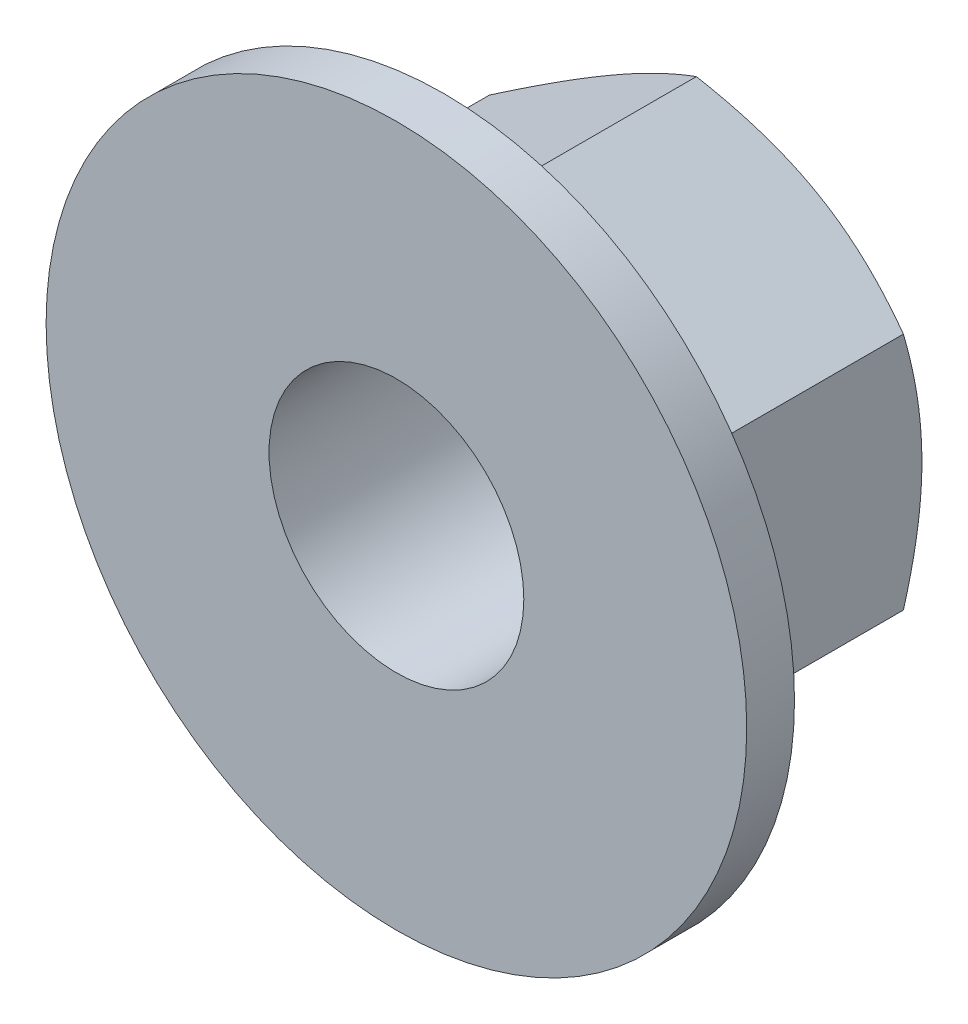
SolidWorks part; units mm, degrees
ref_plane "Plan1" through (0, 0, 0) normal (0, 0, 1) x (1, 0, 0)
ref_plane "Plan2" through (0, 0, 0) normal (0, 1, 0) x (1, 0, 0)
ref_plane "Plan3" through (0, 0, 0) normal (1, 0, 0) x (0, 0, -1)
sketch "Esquisse1" plane through (0, 0, 0) normal (0, 0, 1) x (1, 0, 0)
  line L0 (0, 0) -> (6.5, 0) construction
  line L1 (6.5, -3.7528) -> (6.5, 3.7528)
  line L2 (0, 0) -> (6.5, 3.7528) construction
  line L3 (0, 0) -> (0, 7.5056) construction
  line L4 (6.5, 3.7528) -> (0, 7.5056)
  line L5 (6.5, -3.7528) -> (0, -7.5056)
  line L6 (-6.5, -3.7528) -> (0, -7.5056)
  line L7 (-6.5, -3.7528) -> (-6.5, 3.7528)
  line L8 (-6.5, 3.7528) -> (0, 7.5056)
  circle A0 centre (0, 0) radius 6.5 construction
  circle A1 centre (0, 0) radius 7.5056 construction
  dimension "D2" = 13
  dimension "D1" = 30
extrude "Base-Extrusion" add sketch "Esquisse1" against normal blind 10
sketch "Esquisse2" plane through (0, 0, 0) normal (0, 1, 0) x (1, 0, 0)
  line L1 (0, 10) -> (0, 0) construction
  line L2 (-6.5, 10) -> (-23.8205, 10)
  line L3 (-23.8205, 10) -> (-23.8205, 0)
  line L5 (-23.8205, 0) -> (-6.5, 10)
  line L6 (0, 10) -> (0, 0) construction
  dimension "D1" = 30
revolve "Enlèvement de matière-Révolution1" cut sketch "Esquisse2" angle 360 about L6
sketch "Esquisse3" plane through (0, 0, 0) normal (0, 0, 1) x (1, 0, 0)
  circle A0 centre (0, 0) radius 4
  dimension "D1" = 8
extrude "Enlèv. mat.-Extru.1" cut sketch "Esquisse3" against normal through all
ref_axis "Axe1" through (0, 0, -50) along (0, 0, 1)
sketch "Esquisse4" plane through (0, 0, 0) normal (0, 1, 0) x (1, 0, 0)
  line L0 (-6.5, 0) -> (-11, 0)
  line L1 (-11, 0) -> (-11, 1.5)
  line L2 (-11, 1.5) -> (-8, 3)
  line L4 (-6.5, 3.5) -> (-6.5, 0)
  line L5 (-8, 3) -> (-8, 3.5)
  line L6 (0, 0) -> (0, 10) construction
  line L7 (0, 10) -> (0, 0) construction
  line L8 (-8, 3.5) -> (-6.5, 3.5)
  dimension "D4" = 3
  dimension "D5" = 3.5
  dimension "D1" = 22
  dimension "D2" = 16
  dimension "D3" = 1.5
revolve "Boss.-Révol.1" add sketch "Esquisse4" angle 360 about L6
